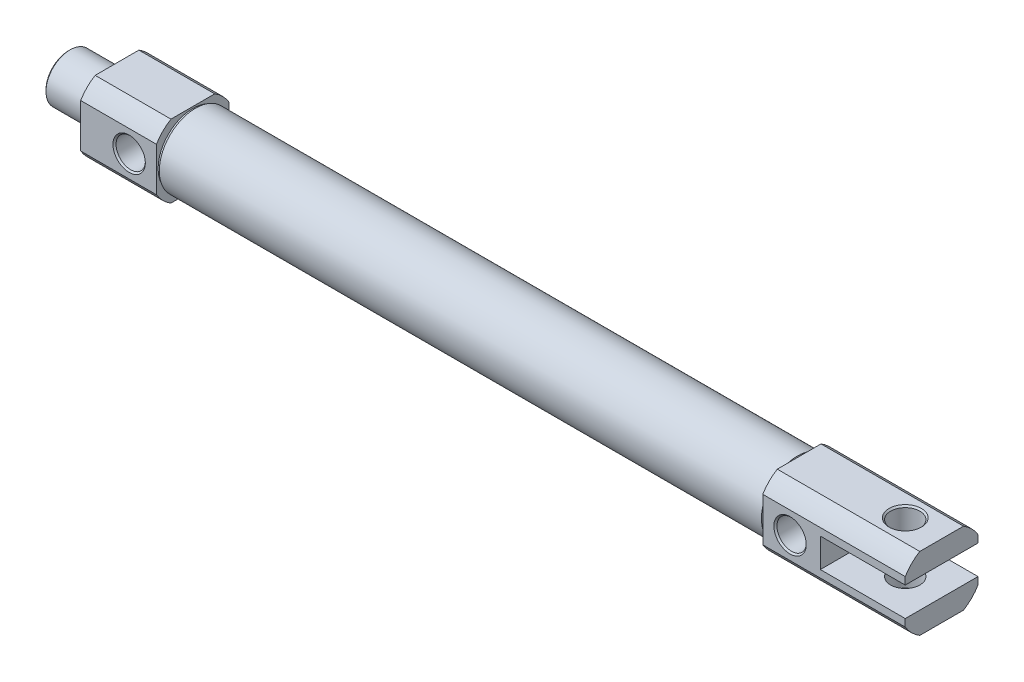
SolidWorks part; units mm, degrees
ref_plane "Front Plane" through (0, 0, 0) normal (0, 0, 1) x (1, 0, 0)
ref_plane "Top Plane" through (0, 0, 0) normal (0, 1, 0) x (1, 0, 0)
ref_plane "Right Plane" through (0, 0, 0) normal (1, 0, 0) x (0, 0, -1)
sketch "Sketch1" plane through (0, 0, 0) normal (1, 0, 0) x (0, 0, -1)
  circle A0 centre (0, 0) radius 5
  circle A1 centre (0, 0) radius 5.97
  dimension "D1" = 10
  dimension "D2" = 11.94
extrude "Boss-Extrude1" add sketch "Sketch1" along normal mid plane 80.4 contours A0 region at (0, 0, 0)
extrude "Boss-Extrude2" add sketch "Sketch1<3>" along normal mid plane 100
sketch "Sketch1<3>" plane through (0, 0, 0) normal (1, 0, 0) x (0, 0, -1) same geometry as "Sketch1"
chamfer "Chamfer1" distance 0.254 angle 60 1 edges at (50, 0, -5.97) first distance on face at (50, 0, -5.97)
chamfer "Chamfer2" distance 0.254 angle 60 1 edges at (-50, 0, -5.97) first distance on face at (-50, 0, -5.97)
sketch "Sketch2" plane through (50, 0, 0) normal (1, 0, 0) x (0, 0, -1)
  line L1 (6, -6) -> (-6, -6)
  line L2 (6, -6) -> (6, 6)
  line L3 (6, 6) -> (-6, 6)
  line L4 (-6, -6) -> (-6, 6)
  line L5 (6, -6) -> (-6, 6) construction
  line L6 (6, 6) -> (-6, -6) construction
  circle A0 centre (0, 0) radius 7
  point P0 (0, 0)
  dimension "D3" = 14
  dimension "D1" = 12
  dimension "D2" = 12
sketch "Sketch3" plane through (50, 0, 0) normal (1, 0, 0) x (0, 0, -1)
  line L0 (-6, 3.6055) -> (-6, -3.6055)
  line L1 (6, 3.6055) -> (6, -3.6055)
  line L2 (-3.6055, 6) -> (3.6055, 6)
  line L3 (-3.6055, -6) -> (3.6055, -6)
  line L4 (6, -6) -> (6, 6) construction
  line L5 (6, 6) -> (-6, 6) construction
  line L6 (-6, -6) -> (-6, 6) construction
  line L7 (6, -6) -> (-6, -6) construction
  arc A0 (-6, 3.6055) -> (-3.6055, 6) centre (0, 0) cw
  arc A1 (6, 3.6055) -> (3.6055, 6) centre (0, 0) ccw
  arc A2 (6, -3.6055) -> (3.6055, -6) centre (0, 0) cw
  arc A3 (-6, -3.6055) -> (-3.6055, -6) centre (0, 0) ccw
  circle A4 centre (0, 0) radius 7 construction
extrude "Boss-Extrude3" add sketch "Sketch3" along normal blind 23.5001
sketch "Sketch5" plane through (0, 6, 0) normal (0, 1, 0) x (1, 0, 0)
  line L0 (73.5001, 3.6055) -> (73.5001, -3.6055) construction
  circle A0 centre (67.5001, 0) radius 2.415
  dimension "D2" = 4.8301
  dimension "D1" = 6
extrude "Cut-Extrude2" cut sketch "Sketch5" against normal through all
sketch "Sketch6" plane through (0, 0, 6) normal (0, 0, 1) x (1, 0, 0)
  line L0 (73.5001, 3.6055) -> (73.5001, -3.6055) construction
  line L1 (59.5001, -2.39) -> (73.5001, -2.39)
  line L2 (59.5001, -2.39) -> (59.5001, 2.39)
  line L3 (59.5001, 2.39) -> (73.5001, 2.39)
  line L4 (73.5001, -2.39) -> (73.5001, 2.39)
  line L5 (59.5001, -2.39) -> (73.5001, 2.39) construction
  line L6 (59.5001, 2.39) -> (73.5001, -2.39) construction
  point P0 (66.5001, 0)
  dimension "D1" = 14
  dimension "D2" = 4.78
extrude "Cut-Extrude3" cut sketch "Sketch6" against normal through all
extrude "Boss-Extrude4" add sketch "Sketch3<2>" against normal blind 12.5001 from surface starting at face at (-50, 0, -5.716)
sketch "Sketch3<2>" plane through (50, 0, 0) normal (1, 0, 0) x (0, 0, -1) same geometry as "Sketch3"
sketch "Sketch4" plane through (0, 0, 6) normal (0, 0, 1) x (1, 0, 0)
  line L0 (50, 3.6055) -> (50, -3.6055) construction
  line L1 (-50, 3.6055) -> (-50, -3.6055) construction
  circle A0 centre (54.5001, 0) radius 2.415
  circle A1 centre (-54.5001, 0) radius 2.415
  dimension "D2" = 4.8301
  dimension "D1" = 4.5001
  dimension "D3" = 4.5001
extrude "Cut-Extrude4" cut sketch "Sketch4" against normal blind 6
sketch "Sketch8" plane through (-62.5001, 0, 0) normal (-1, 0, 0) x (0, 0, 1)
  circle A0 centre (0, 0) radius 3.9688
  circle A1 centre (0, 0) radius 2.1827
  dimension "D1" = 4.3655
  dimension "D2" = 7.9375
extrude "Boss-Extrude5" add sketch "Sketch8" along normal blind 8
chamfer "Chamfer5" distance 0.254 angle 45 6 edges at (67.5001, -6, 2.415) (67.5001, 6, 2.415) (56.9151, 0, 6) (-52.0851, 0, 6) (-70.5001, 0, 3.9688) (-70.5001, 0, 2.1827)
equation "\"D2@Sketch2\"=\"D1@Sketch2\""
